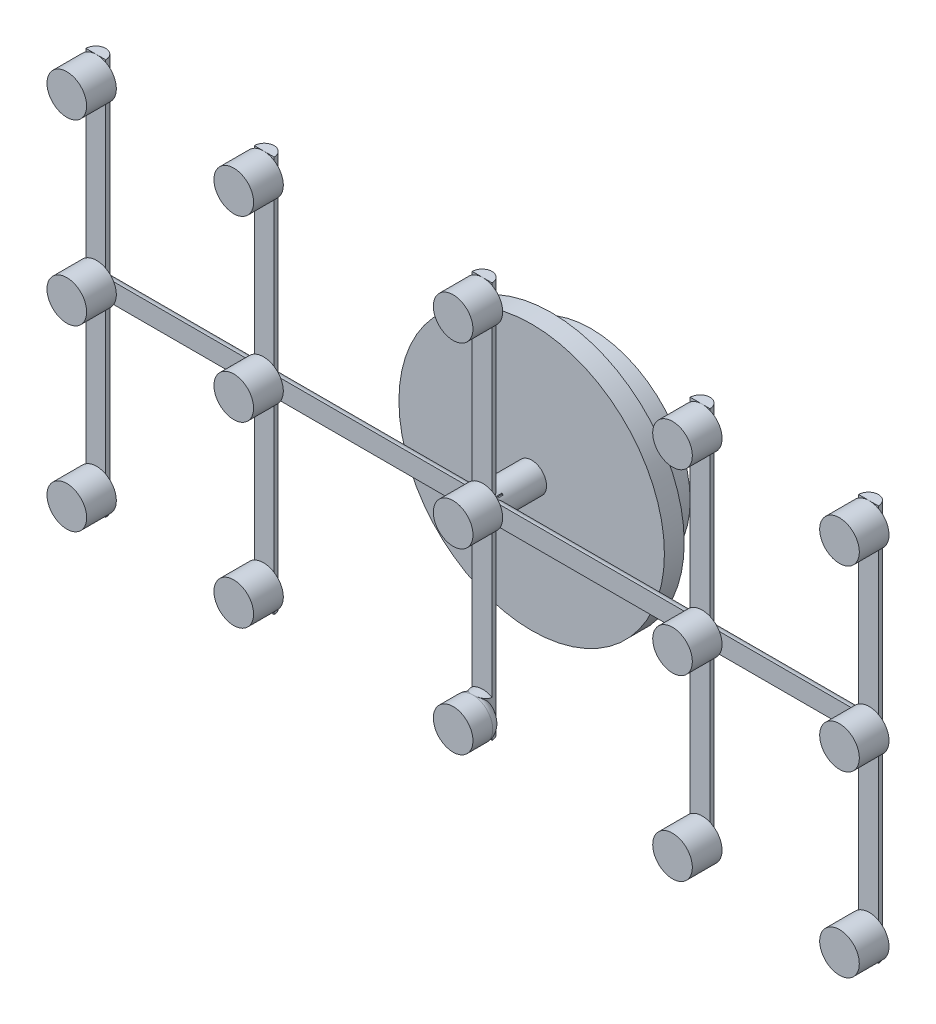
SolidWorks part; units mm, degrees
material "6061-T6 (SS)"
ref_plane "Ebene vorne" through (0, 0, 0) normal (0, 0, 1) x (1, 0, 0)
ref_plane "Ebene oben" through (0, 0, 0) normal (0, 1, 0) x (1, 0, 0)
ref_plane "Ebene rechts" through (0, 0, 0) normal (1, 0, 0) x (0, 0, -1)
sketch "Skizze2" plane through (0, 0, 0) normal (0, 0, 1) x (1, 0, 0)
  circle A0 centre (0, 0) radius 50
  dimension "D1" = 100
extrude "Aufsatz-Linear austragen1" add sketch "Skizze2" along normal blind 20
sketch "Skizze3" plane through (0, 0, 20) normal (0, 0, 1) x (1, 0, 0)
  circle A0 centre (0, 0) radius 67
  dimension "D1" = 134
extrude "Aufsatz-Linear austragen2" add sketch "Skizze3" along normal blind 10
sketch "Skizze4" plane through (0, 0, 30) normal (0, 0, 1) x (1, 0, 0)
  line L1 (-200, -100) -> (200, -100)
  line L2 (-200, -100) -> (-200, 100)
  line L3 (-200, 100) -> (200, 100)
  line L4 (200, -100) -> (200, 100)
  line L5 (-200, -100) -> (200, 100) construction
  line L6 (-200, 100) -> (200, -100) construction
  point P0 (0, 0)
  dimension "D1" = 200
  dimension "D2" = 400
sketch "Skizze5" plane through (0, 0, 30) normal (0, 0, 1) x (1, 0, 0)
  circle A0 centre (0, 0) radius 7.5
  dimension "D1" = 15
extrude "Aufsatz-Linear austragen3" add sketch "Skizze5" along normal blind 20
sketch "Skizze6" plane through (0, 0, 50) normal (0, 0, 1) x (1, 0, 0)
  line L0 (200, -100) -> (200, 100) construction
  line L1 (-200, 5) -> (200, 5)
  line L2 (-200, 5) -> (-200, -5)
  line L3 (-200, -5) -> (200, -5)
  line L4 (200, 5) -> (200, -5)
  line L5 (-200, 5) -> (200, -5) construction
  line L6 (-200, -5) -> (200, 5) construction
  point P0 (0, 0)
  dimension "D1" = 10
extrude "Aufsatz-Linear austragen4" add sketch "Skizze6" along normal blind 5
sketch "Skizze7" plane through (0, 0, 50) normal (0, 0, 1) x (1, 0, 0)
  line L0 (-200, 100) -> (200, 100) construction
  line L1 (-5, -100) -> (5, -100)
  line L2 (-5, -100) -> (-5, 100)
  line L3 (-5, 100) -> (5, 100)
  line L4 (5, -100) -> (5, 100)
  line L5 (-5, -100) -> (5, 100) construction
  line L6 (-5, 100) -> (5, -100) construction
  point P0 (0, 0)
  dimension "D1" = 10
extrude "Aufsatz-Linear austragen5" add sketch "Skizze7" along normal up to surface (5 mm away) up to face at (0, 0, 55)
sketch "Skizze8" plane through (0, 0, 50) normal (0, 0, 1) x (1, 0, 0)
  line L0 (-200, 100) -> (200, 100) construction
  line L1 (-115, -100) -> (-105, -100)
  line L2 (-115, -100) -> (-115, 100)
  line L3 (-115, 100) -> (-105, 100)
  line L4 (-105, -100) -> (-105, 100)
  line L5 (-115, -100) -> (-105, 100) construction
  line L6 (-115, 100) -> (-105, -100) construction
  line L7 (-5, 100) -> (-5, 5) construction
  line L9 (0, 0) -> (0, 100) construction
  line L10 (-200, 100) -> (200, -100) construction
  line L11 (115, -100) -> (105, -100)
  line L12 (115, 100) -> (105, 100)
  line L13 (115, -100) -> (115, 100)
  line L14 (105, -100) -> (105, 100)
  line L15 (-200, -100) -> (-200, 100) construction
  line L16 (-200, -100) -> (-190, -100)
  line L17 (-200, -100) -> (-200, 100)
  line L18 (-200, 100) -> (-190, 100)
  line L19 (-190, -100) -> (-190, 100)
  line L20 (-200, -100) -> (-190, 100) construction
  line L21 (-200, 100) -> (-190, -100) construction
  line L22 (200, -100) -> (190, -100)
  line L23 (190, -100) -> (190, 100)
  line L24 (200, -100) -> (200, 100)
  line L25 (200, 100) -> (190, 100)
  point P0 (-110, 0)
  point P17 (-195, 0)
  dimension "D1" = 10
  dimension "D2" = 100
  dimension "D3" = 10
  dimension "D4" = 0
extrude "Aufsatz-Linear austragen6" add sketch "Skizze8" along normal up to surface (5 mm away) up to face at (0, 0, 55)
sketch "Skizze9" plane through (0, 0, 55) normal (0, 0, 1) x (1, 0, 0)
  line L0 (-200, 0) -> (0, 0) construction
  line L1 (-200, -100) -> (-200, 100) construction
  line L2 (-194.6359, 100) -> (-194.6359, -100) construction
  line L3 (-200, 100) -> (200, 100) construction
  line L4 (-200, -100) -> (200, -100) construction
  line L5 (-152.5, 5) -> (-152.5, 100) construction
  line L6 (-115, 5) -> (-190, 5) construction
  line L7 (-55, 5) -> (-55, 100) construction
  line L8 (-5, 5) -> (-105, 5) construction
  line L9 (0.3641, 0) -> (0.3641, 100) construction
  circle A1 centre (-194.6359, 90) radius 10
  circle A2 centre (-194.6359, 0) radius 10
  circle A3 centre (-110.3641, 0) radius 10
  circle A4 centre (-110.3641, 90) radius 10
  circle A5 centre (0.3641, 0) radius 10
  circle A6 centre (0.3641, 90) radius 10
  circle A7 centre (111.0924, 0) radius 10
  circle A8 centre (111.0924, 90) radius 10
  circle A9 centre (195.3641, 0) radius 10
  circle A10 centre (195.3641, 90) radius 10
  circle A11 centre (195.3641, -90) radius 10
  circle A12 centre (111.0924, -90) radius 10
  circle A13 centre (0.3641, -90) radius 10
  circle A14 centre (-110.3641, -90) radius 10
  circle A15 centre (-194.6359, -90) radius 10
  dimension "D1" = 20
  dimension "D3" = 20
  dimension "D2" = 10
extrude "Aufsatz-Linear austragen7" add sketch "Skizze9" along normal blind 15
fillet "Verrundung5" radius 5 26 edges at (-190, -52.5, 50) (-200, 0, 50) (190, 52.5, 50) (190, -52.5, 50) (200, 0, 50) (152.5, -5, 50) (152.5, 5, 50) (115, 52.5, 50) (105, 52.5, 50) (105, -52.5, 50) (115, -52.5, 50) (55.2951, -5, 50) (55.2951, 5, 50) (-5, 52.7951, 50) (5, 52.7951, 50) (-5, -52.7951, 50) (5, -52.7951, 50) (-152.5, 5, 50) (-152.5, -5, 50) (-55.2951, 5, 50) (-55.2951, -5, 50) (-105, 52.5, 50) (-115, 52.5, 50) (-115, -52.5, 50) (-105, -52.5, 50) (-190, 52.5, 50)
fillet "Verrundung6" radius 5 1 edges at (-9.6359, -90, 55)
